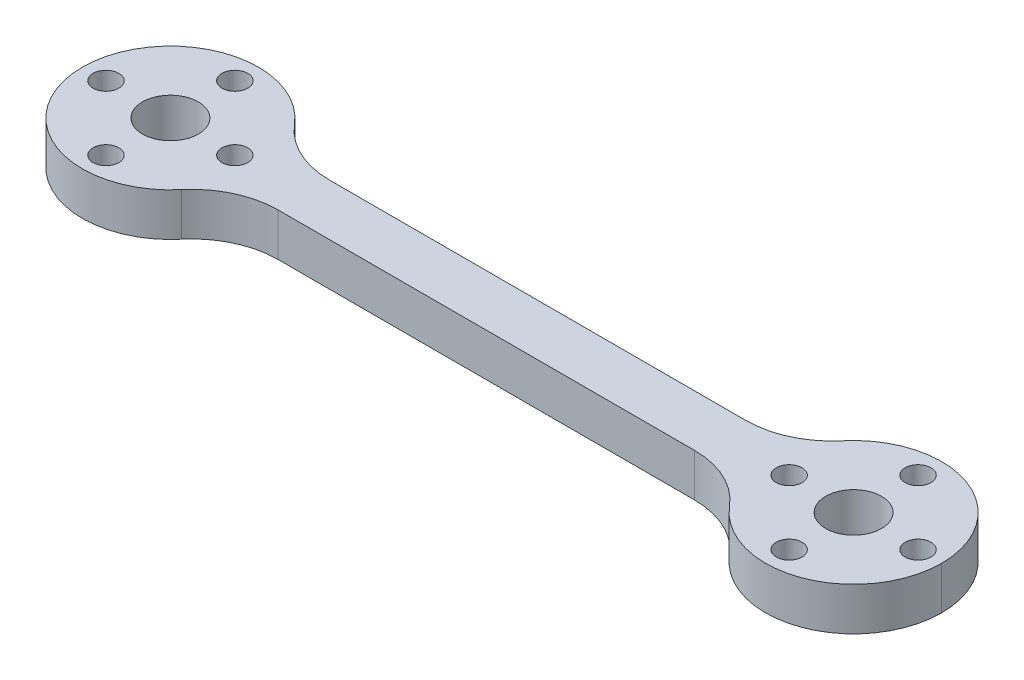
SolidWorks part; units mm, degrees
ref_plane "Front Plane" through (0, 0, 0) normal (0, 0, 1) x (1, 0, 0)
ref_plane "Top Plane" through (0, 0, 0) normal (0, 1, 0) x (1, 0, 0)
ref_plane "Right Plane" through (0, 0, 0) normal (1, 0, 0) x (0, 0, -1)
sketch "Sketch1" plane through (0, 0, 0) normal (0, 1, 0) x (1, 0, 0)
  line L0 (0, 10.25) -> (100, 10.25) construction
  line L1 (0, 0) -> (100, 0)
  line L2 (0, 0) -> (0, 20.5)
  line L3 (0, 20.5) -> (100, 20.5)
  line L4 (100, 0) -> (100, 20.5)
  line L5 (50, 20.5) -> (50, 0) construction
  line L6 (10.25, 10.25) -> (16.2336, 16.2336) construction
  line L7 (10.25, 10.25) -> (15.5852, 4.9148) construction
  circle A0 centre (10.25, 10.25) radius 3.25
  circle A1 centre (17.75, 10.25) radius 1.5
  circle A2 centre (10.25, 17.75) radius 1.5
  circle A3 centre (10.25, 2.75) radius 1.5
  circle A4 centre (2.75, 10.25) radius 1.5
  circle A5 centre (82.25, 10.25) radius 1.5
  circle A6 centre (89.75, 17.75) radius 1.5
  circle A7 centre (89.75, 2.75) radius 1.5
  circle A8 centre (97.25, 10.25) radius 1.5
  circle A9 centre (89.75, 10.25) radius 3.25
  dimension "D3" = 6.5
  dimension "D4" = 3
  dimension "D6" = 7.5
  dimension "D1" = 100
  dimension "D2" = 20.5
  dimension "D5" = 10.25
extrude "Boss-Extrude1" add sketch "Sketch1" along normal blind 5
fillet "Fillet1" radius 10.25 4 edges at (0, 2.5, 0) (0, 2.5, -20.5) (100, 2.5, -20.5) (100, 2.5, 0)
sketch "Sketch2" plane through (0, 5, 0) normal (0, 1, 0) x (1, 0, 0)
  line L0 (50, 20.5) -> (50, 0) construction
  line L1 (89.75, 20.5) -> (10.25, 20.5) construction
  line L2 (10.25, 0) -> (89.75, 0) construction
  line L3 (0, 10.25) -> (100, 10.25) construction
  line L4 (10.25, 20.5) -> (10.25, 10.25) construction
  line L5 (20.0511, 13.25) -> (79.9489, 13.25)
  line L6 (10.25, 20.5) -> (89.75, 20.5)
  line L7 (20.0511, 7.25) -> (79.9489, 7.25)
  line L8 (10.25, 0) -> (89.75, 0)
  arc A0 (10.25, 0) -> (20.0511, 7.25) centre (10.25, 10.25) ccw
  arc A1 (79.9489, 13.25) -> (89.75, 20.5) centre (89.75, 10.25) cw
  arc A2 (20.0511, 13.25) -> (10.25, 20.5) centre (10.25, 10.25) ccw
  arc A3 (89.75, 0) -> (79.9489, 7.25) centre (89.75, 10.25) cw
  point P24 (50, 13.25)
  point P25 (50, 7.25)
  dimension "D1" = 3
extrude "Cut-Extrude1" cut sketch "Sketch2" against normal blind 10
fillet "Fillet2" radius 10 4 edges at (79.9489, 2.5, -13.25) (79.9489, 2.5, -7.25) (20.0511, 2.5, -7.25) (20.0511, 2.5, -13.25)
